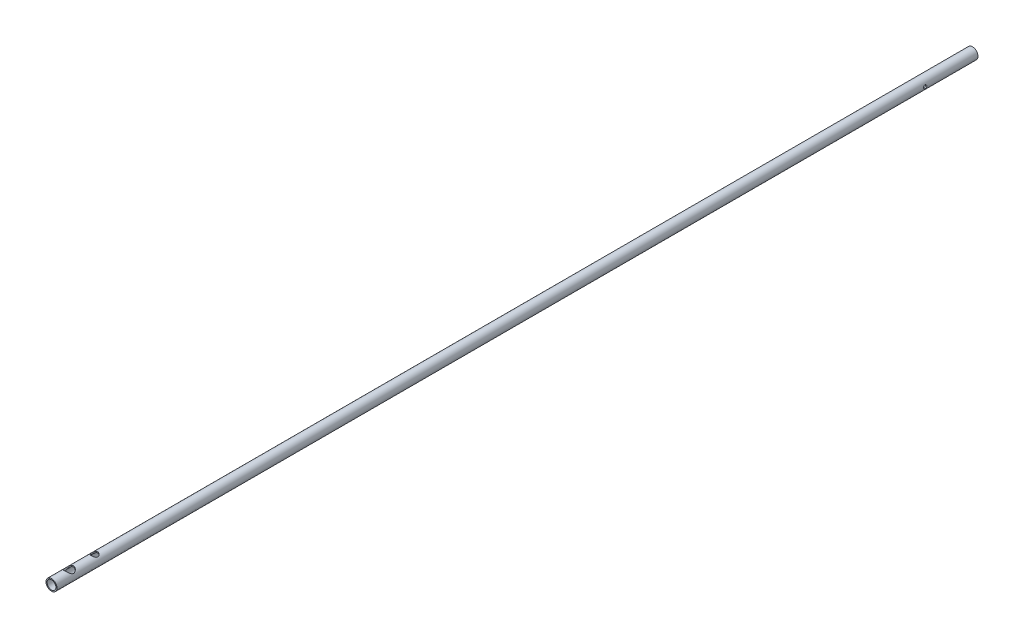
SolidWorks part; units mm, degrees
material "1060 合金"
ref_plane "正面" through (0, 0, 0) normal (0, 0, 1) x (1, 0, 0)
ref_plane "平面" through (0, 0, 0) normal (0, 1, 0) x (1, 0, 0)
ref_plane "右側面" through (0, 0, 0) normal (1, 0, 0) x (0, 0, -1)
sketch "ｽｹｯﾁ1" plane through (0, 0, 0) normal (0, 0, 1) x (1, 0, 0)
  circle A0 centre (0, 0) radius 5
  dimension "D1" = 10
extrude "押し出し-薄板1" add sketch "ｽｹｯﾁ1" along normal blind 836.5 thin thin type one direction reverse wall 1
sketch "ｽｹｯﾁ2" plane through (0, 0, 0) normal (0, 1, 0) x (1, 0, 0)
  line L0 (0, 0) -> (0, 50000) construction
  line L1 (-5, -836.5) -> (5, -836.5) construction
  circle A0 centre (0, -820.5) radius 2
  circle A1 centre (0, -797.5) radius 1.5
  circle A2 centre (0, -820.5) radius 4
  circle A3 centre (0, -797.5) radius 3
  dimension "D1" = 16
  dimension "D2" = 23
  dimension "D3" = 4
  dimension "D4" = 8
  dimension "D5" = 6
  dimension "D6" = 3
extrude "ｶｯﾄ - 押し出し1" cut sketch "ｽｹｯﾁ2" against normal through all both and the other way through all contours L0 A1 | A1 L0 | L0 A0 | A0 L0 region at (0, 0, 820.5) region at (0, 0, 797.5)
extrude "ｶｯﾄ - 押し出し2" cut sketch "ｽｹｯﾁ2<3>" along normal through all contours A2 | A3
sketch "ｽｹｯﾁ2<3>" plane through (0, 0, 0) normal (0, 1, 0) x (1, 0, 0) same geometry as "ｽｹｯﾁ2"
sketch "ｽｹｯﾁ3" plane through (0, 0, 0) normal (1, 0, 0) x (0, 0, -1)
  line L0 (0, 0) -> (50000, 0) construction
  line L1 (0, -5) -> (0, 5) construction
  circle A0 centre (-48, 0) radius 1.5
  circle A1 centre (-48, 0) radius 3
  dimension "D1" = 48
  dimension "D2" = 3
  dimension "D3" = 6
extrude "ｶｯﾄ - 押し出し3" cut sketch "ｽｹｯﾁ3" against normal through all both and the other way through all contours A0
extrude "ｶｯﾄ - 押し出し4" cut sketch "ｽｹｯﾁ3<3>" against normal blind 10 contours A1
sketch "ｽｹｯﾁ3<3>" plane through (0, 0, 0) normal (1, 0, 0) x (0, 0, -1) same geometry as "ｽｹｯﾁ3"
